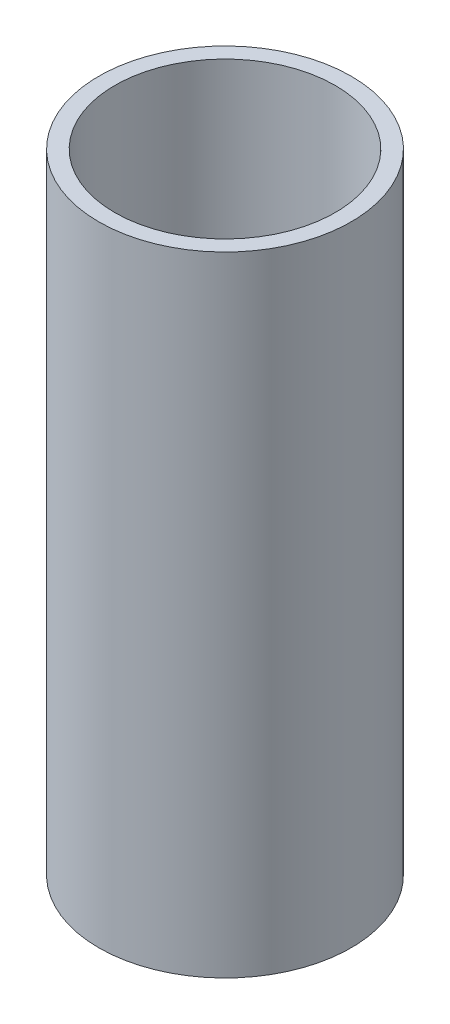
SolidWorks part; units mm, degrees
material "Rubber"
ref_plane "Front Plane" through (0, 0, 0) normal (0, 0, 1) x (1, 0, 0)
ref_plane "Top Plane" through (0, 0, 0) normal (0, 1, 0) x (1, 0, 0)
ref_plane "Right Plane" through (0, 0, 0) normal (1, 0, 0) x (0, 0, -1)
sketch "Sketch1" plane through (0, 0, 0) normal (0, 1, 0) x (1, 0, 0)
  circle A0 centre (0, 0) radius 6.135
  circle A1 centre (0, 0) radius 7.025
extrude "Boss-Extrude1" add sketch "Sketch1" along normal blind 35
